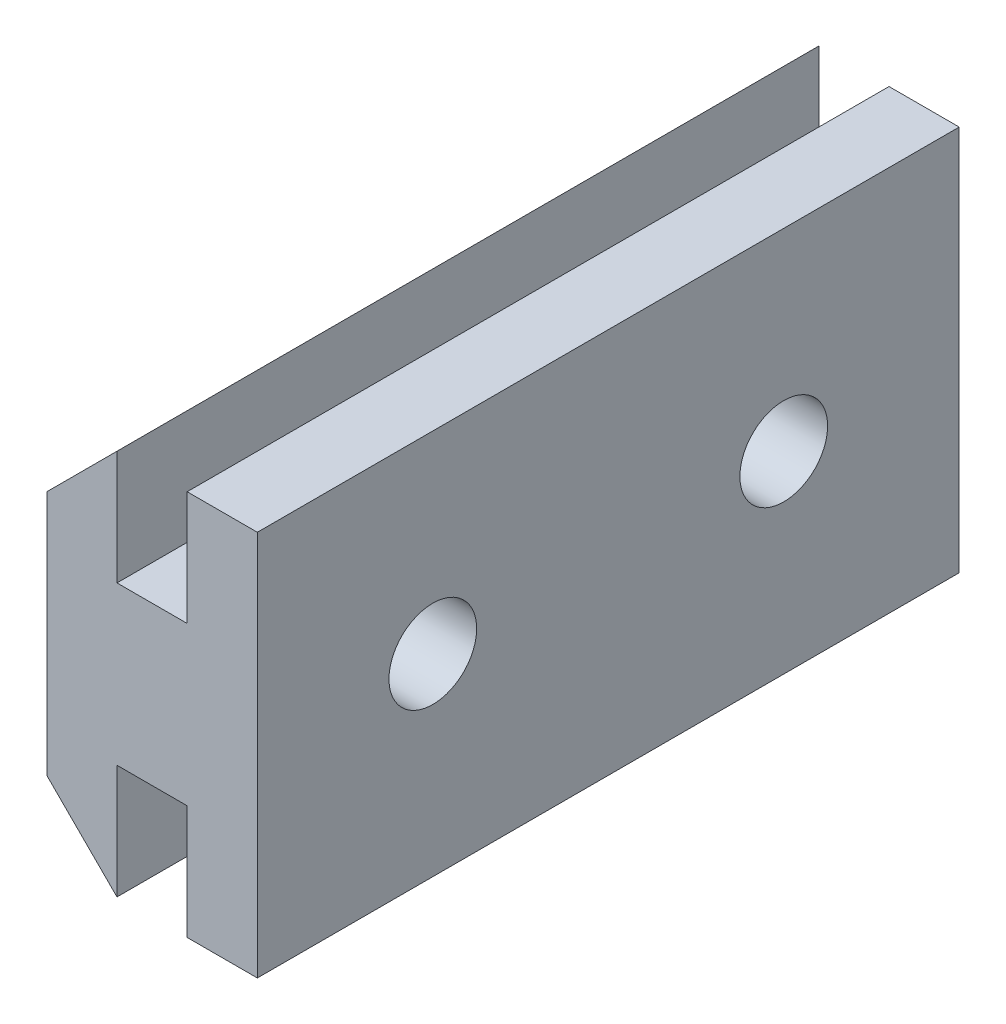
SolidWorks part; units mm, degrees
ref_plane "Plan de face" through (0, 0, 0) normal (0, 0, 1) x (1, 0, 0)
ref_plane "Plan de dessus" through (0, 0, 0) normal (0, 1, 0) x (1, 0, 0)
ref_plane "Plan de droite" through (0, 0, 0) normal (1, 0, 0) x (0, 0, -1)
sketch "ProfileRainureEsquisse" plane through (0, 0, 0) normal (0, 0, 1) x (1, 0, 0)
  line L0 (-0.4, -1.25) -> (-0.4, 5.75)
  line L1 (-0.4, 5.75) -> (1.6, 7.75)
  line L2 (-0.4, -1.25) -> (1.6, -3.25)
  line L3 (1.6, 7.75) -> (1.6, 4.5)
  line L4 (1.6, 4.5) -> (3.6, 4.5)
  line L5 (3.6, 4.5) -> (3.6, 7.75)
  line L6 (3.6, 0) -> (1.6, 0)
  line L7 (1.6, 0) -> (1.6, -3.25)
  line L8 (3.6, 7.75) -> (5.6, 7.75)
  line L9 (5.6, 7.75) -> (5.6, -3.25)
  line L10 (5.6, -3.25) -> (3.6, -3.25)
  line L11 (3.6, -3.25) -> (3.6, 0)
  dimension "D1" = 2
  dimension "D2" = 2
  dimension "D3" = 11
  dimension "D4" = 4.5
  dimension "D5" = 2
  dimension "D6" = 45
extrude "Boss.-Extru.1" add sketch "ProfileRainureEsquisse" along normal blind 20
sketch "Esquisse1" plane through (5.6, 0, 0) normal (1, 0, 0) x (0, 0, -1)
  line L0 (-20, -3.25) -> (-20, 7.75) construction
  line L1 (0, -3.25) -> (0, 7.75) construction
  circle A0 centre (-15, 2.25) radius 1.25
  circle A1 centre (-5, 2.25) radius 1.25
  point P2 (-20, 2.25)
  point P3 (0, 2.25)
  dimension "D1" = 2.5
  dimension "D3" = 2.5
  dimension "D2" = 5
  dimension "D4" = 5
extrude "Enlèv. mat.-Extru.1" cut sketch "Esquisse1" against normal through all
